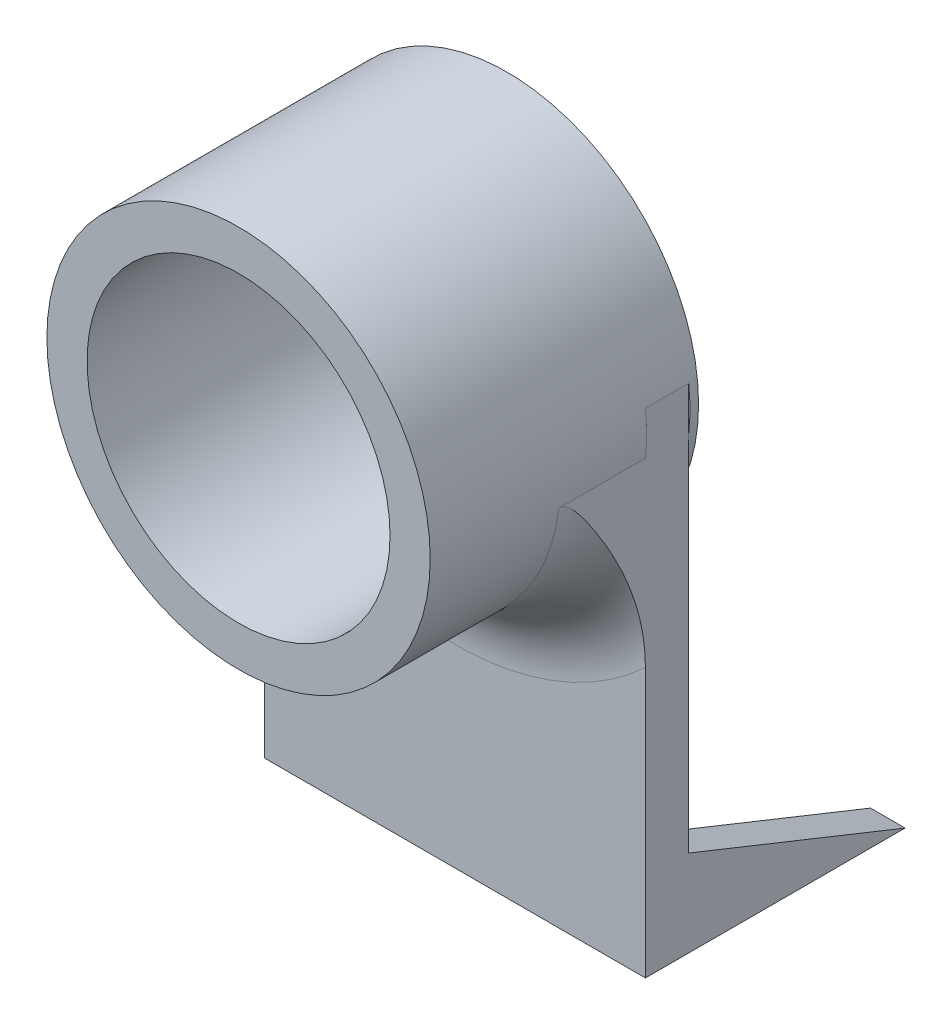
SolidWorks part; units mm, degrees
material "ABS"
ref_plane "Plan de face" through (0, 0, 0) normal (0, 0, 1) x (1, 0, 0)
ref_plane "Plan de dessus" through (0, 0, 0) normal (0, 1, 0) x (1, 0, 0)
ref_plane "Plan de droite" through (0, 0, 0) normal (1, 0, 0) x (0, 0, -1)
sketch "Esquisse1" plane through (0, 0, 0) normal (0, 0, 1) x (1, 0, 0)
  line L0 (0, 0) -> (0, -57)
  line L1 (0, -57) -> (44, -57)
  line L2 (44, -57) -> (44, 0)
  arc A0 (0, 0) -> (44, 0) centre (22, -2.5) cw
  circle A1 centre (22, -2.5) radius 17.5
  dimension "D4" = 35
  dimension "D1" = 57
  dimension "D2" = 44
  dimension "D3" = 2.5
extrude "Boss.-Extru.1" add sketch "Esquisse1" along normal blind 5
sketch "Esquisse2" plane through (0, 0, 5) normal (0, 0, 1) x (1, 0, 0)
  circle A0 centre (22, -2.5) radius 17.5
  circle A1 centre (22, -2.5) radius 22.1416
extrude "Boss.-Extru.2" add sketch "Esquisse2" along normal blind 25
fillet "Congé1" radius 10 1 edges at (22, -24.6416, 5)
sketch "Esquisse3" plane through (44, 0, 0) normal (1, 0, 0) x (0, 0, -1)
  line L0 (0, -47) -> (25, -57)
  line L1 (0, -57) -> (0, 0) construction
  line L2 (25, -57) -> (0, -57)
  line L3 (0, -57) -> (0, -47)
  dimension "D1" = 10
  dimension "D2" = 25
extrude "Boss.-Extru.3" add sketch "Esquisse3" against normal blind 4
sketch "Esquisse4" plane through (0, 0, 0) normal (-1, 0, 0) x (0, 0, 1)
  line L0 (0, -57) -> (-25, -57)
  line L1 (-25, -57) -> (0, -47)
  line L2 (0, 0) -> (0, -57) construction
  line L3 (0, -47) -> (0, -57)
  dimension "D1" = 10
  dimension "D2" = 25
extrude "Boss.-Extru.4" add sketch "Esquisse4" against normal blind 4 separate body
sketch "Esquisse5" plane through (0, 0, 0) normal (0, 0, -1) x (-1, 0, 0)
  circle A0 centre (-22, -2.5) radius 22.1416
extrude "Boss.-Extru.5" add sketch "Esquisse5" along normal blind 1
sketch "Esquisse6" plane through (0, 0, -1) normal (0, 0, -1) x (-1, 0, 0)
  line L0 (-22, -2.5) -> (-12.36, -2.5) construction
  circle A0 centre (-12.36, -2.5) radius 1.25
  circle A1 centre (-22, -12.14) radius 1.25
  circle A2 centre (-31.64, -2.5) radius 1.25
  circle A3 centre (-22, 7.14) radius 1.25
  point P13 (-22, -2.5)
  dimension "D2" = 2.5
  dimension "D1" = 9.64
  dimension "D3" = 4
extrude "Enlèv. mat.-Extru.1" cut sketch "Esquisse6" against normal through all
